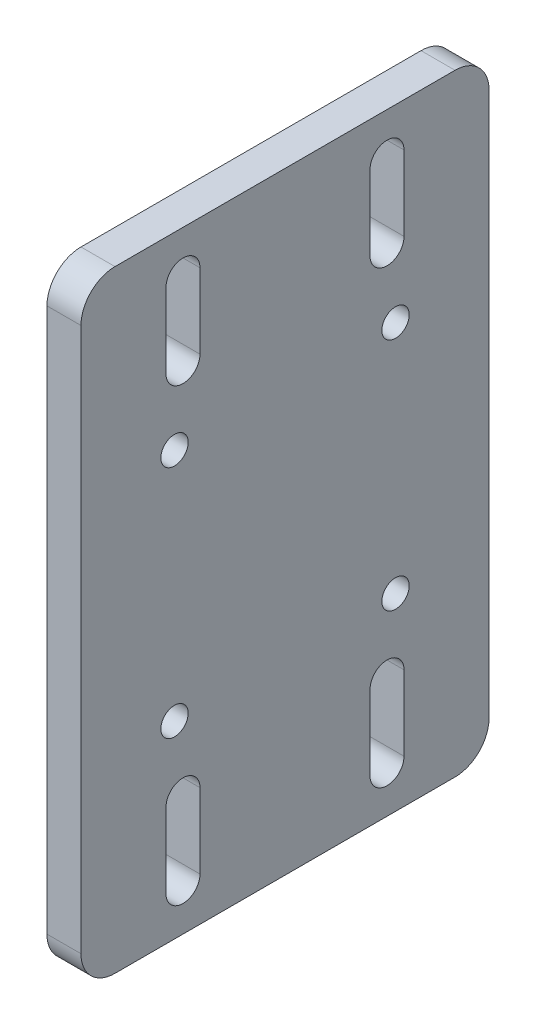
SolidWorks part; units mm, degrees
ref_plane "Front Plane" through (0, 0, 0) normal (0, 0, 1) x (1, 0, 0)
ref_plane "Top Plane" through (0, 0, 0) normal (0, 1, 0) x (1, 0, 0)
ref_plane "Right Plane" through (0, 0, 0) normal (1, 0, 0) x (0, 0, -1)
sketch "Sketch1" plane through (0, 0, 0) normal (1, 0, 0) x (0, 0, -1)
  line L1 (-38.1, -57.15) -> (38.1, -57.15)
  line L2 (-38.1, -57.15) -> (-38.1, 57.15)
  line L3 (-38.1, 57.15) -> (38.1, 57.15)
  line L4 (38.1, -57.15) -> (38.1, 57.15)
  line L5 (-38.1, -57.15) -> (38.1, 57.15) construction
  line L6 (-38.1, 57.15) -> (38.1, -57.15) construction
  point P0 (0, 0)
  point P5 (0, 0)
  dimension "D1" = 76.2
  dimension "D2" = 114.3
extrude "Boss-Extrude1" add sketch "Sketch1" along normal blind 6.35
hole_wizard "1/4-20 Tapped Hole1" positions "Sketch2" profile "Sketch3" tap size "1/4-20" standard "ANSI Inch" end condition through all
sketch "Sketch2" plane through (6.35, 0, 0) normal (1, 0, 0) x (0, 0, -1)
  line L1 (-20.6375, -21.9075) -> (20.6375, -21.9075) construction
  line L2 (-20.6375, -21.9075) -> (-20.6375, 21.9075) construction
  line L3 (-20.6375, 21.9075) -> (20.6375, 21.9075) construction
  line L4 (20.6375, -21.9075) -> (20.6375, 21.9075) construction
  line L5 (-20.6375, -21.9075) -> (20.6375, 21.9075) construction
  line L6 (-20.6375, 21.9075) -> (20.6375, -21.9075) construction
  point P0 (-20.6375, 21.9075)
  point P58 (20.6375, 21.9075)
  point P61 (20.6375, -21.9075)
  point P64 (-20.6375, -21.9075)
  dimension "D1" = 43.815
  dimension "D2" = 41.275
cosmetic thread "Hole Thread1" parameters "D2"=6.35
cosmetic thread "Hole Thread2" parameters "D2"=6.35
cosmetic thread "Hole Thread3" parameters "D2"=6.35
cosmetic thread "Hole Thread4" parameters "D2"=6.35
sketch "Sketch3" plane through (6.35, 21.9075, 20.6375) normal (0, 1, 0) x (0, 0, -1)
  line L0 (0, 0) -> (0, 6.35)
  line L1 (0, 6.35) -> (2.5527, 6.35)
  line L2 (2.5527, 6.35) -> (2.5527, 0)
  line L5 (2.5527, 0) -> (0, 0)
  line L11 (0, -6.35) -> (0, 107.95) construction
  dimension "Thru Tap Drill Dia." = 5.1054
  dimension "Thru Tap Drill Depth" = 6.35
sketch "Sketch4" plane through (6.35, 0, 0) normal (1, 0, 0) x (0, 0, -1)
  line L5 (19.05, 29.972) -> (19.05, 57.15) construction
  line L6 (38.1, 57.15) -> (-38.1, 57.15) construction
  line L7 (0, -57.15) -> (0, 57.15) construction
  line L8 (-29.972, 29.972) -> (29.972, 29.972) construction
  line L9 (-29.972, 29.972) -> (-29.972, -29.972) construction
  line L10 (-29.972, -29.972) -> (29.972, -29.972) construction
  line L11 (29.972, 29.972) -> (29.972, -29.972) construction
  line L12 (-29.972, 29.972) -> (29.972, -29.972) construction
  line L13 (-29.972, -29.972) -> (29.972, 29.972) construction
  line L14 (-38.1, -57.15) -> (38.1, -57.15) construction
  line L15 (-38.1, 0) -> (38.1, 0) construction
  line L16 (15.875, 49.022) -> (22.225, 49.022) construction
  line L17 (15.875, 49.022) -> (15.875, 35.052)
  line L18 (15.875, 35.052) -> (22.225, 35.052) construction
  line L19 (22.225, 49.022) -> (22.225, 35.052)
  line L20 (15.875, 49.022) -> (22.225, 35.052) construction
  line L21 (15.875, 35.052) -> (22.225, 49.022) construction
  line L22 (-38.1, 57.15) -> (-38.1, -57.15) construction
  line L23 (38.1, -57.15) -> (38.1, 57.15) construction
  line L24 (-15.875, 35.052) -> (-22.225, 49.022) construction
  line L25 (-15.875, 49.022) -> (-22.225, 35.052) construction
  line L26 (-15.875, 35.052) -> (-22.225, 35.052) construction
  line L27 (-15.875, 49.022) -> (-22.225, 49.022) construction
  line L28 (-22.225, 49.022) -> (-22.225, 35.052)
  line L29 (-15.875, 49.022) -> (-15.875, 35.052)
  line L30 (-15.875, -49.022) -> (-22.225, -49.022) construction
  line L31 (-15.875, -35.052) -> (-22.225, -35.052) construction
  line L32 (-15.875, -49.022) -> (-22.225, -35.052) construction
  line L33 (-15.875, -35.052) -> (-22.225, -49.022) construction
  line L34 (15.875, -35.052) -> (22.225, -49.022) construction
  line L35 (15.875, -49.022) -> (22.225, -35.052) construction
  line L36 (15.875, -35.052) -> (22.225, -35.052) construction
  line L37 (15.875, -49.022) -> (22.225, -49.022) construction
  line L38 (-15.875, -49.022) -> (-15.875, -35.052)
  line L39 (-22.225, -49.022) -> (-22.225, -35.052)
  line L40 (22.225, -49.022) -> (22.225, -35.052)
  line L41 (15.875, -49.022) -> (15.875, -35.052)
  line L42 (11.0908, 31.877) -> (29.972, 31.877) construction
  arc A0 (15.875, 49.022) -> (22.225, 49.022) centre (19.05, 49.022) cw
  arc A1 (22.225, 35.052) -> (15.875, 35.052) centre (19.05, 35.052) cw
  arc A2 (-22.225, 35.052) -> (-15.875, 35.052) centre (-19.05, 35.052) ccw
  arc A3 (-15.875, 49.022) -> (-22.225, 49.022) centre (-19.05, 49.022) ccw
  arc A4 (-15.875, -49.022) -> (-22.225, -49.022) centre (-19.05, -49.022) cw
  arc A5 (-22.225, -35.052) -> (-15.875, -35.052) centre (-19.05, -35.052) cw
  arc A6 (22.225, -35.052) -> (15.875, -35.052) centre (19.05, -35.052) ccw
  arc A7 (15.875, -49.022) -> (22.225, -49.022) centre (19.05, -49.022) ccw
  point P7 (0, 0)
  point P13 (19.05, 42.037)
  point P33 (-19.05, 42.037)
  point P46 (-19.05, -42.037)
  point P47 (19.05, -42.037)
  dimension "D4" = 19.05
  dimension "D1" = 13.97
  dimension "D2" = 59.944
  dimension "D3" = 6.35
  dimension "D5" = 1.905
extrude "Cut-Extrude1" cut sketch "Sketch4" against normal through all
ref_axis "Axis1" through (0, 0, 0) along (1, 0, 0)
fillet "Fillet1" radius 6.35 4 edges at (3.175, -57.15, 38.1) (3.175, -57.15, -38.1) (3.175, 57.15, -38.1) (3.175, 57.15, 38.1)
